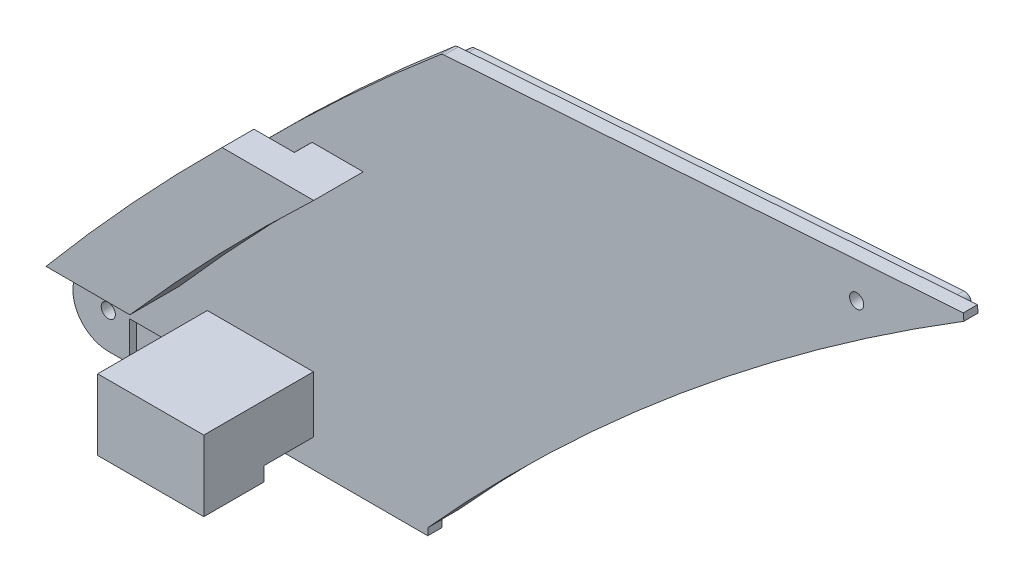
SolidWorks part; units mm, degrees
ref_plane "Front Plane" through (0, 0, 0) normal (0, 0, 1) x (1, 0, 0)
ref_plane "Top Plane" through (0, 0, 0) normal (0, 1, 0) x (1, 0, 0)
ref_plane "Right Plane" through (0, 0, 0) normal (1, 0, 0) x (0, 0, -1)
sketch "Sketch6" plane through (0, 0, 2) normal (0, 0, 1) x (1, 0, 0)
  line L0 (-47.1688, -59) -> (-2.4436, -59) construction
  line L1 (69.7935, 3.878) -> (0.7233, -0.9519) construction
  line L2 (-47.1688, -59) -> (-2.4436, -59)
  line L3 (69.7935, 3.878) -> (0.7233, -0.9519)
  line L4 (-47.1688, -58) -> (-2.4436, -58)
  line L5 (69.8632, 2.8804) -> (0.793, -1.9494)
  arc A0 (-2.4436, -59) -> (-1.7027, -58.6716) centre (-2.4436, -58) ccw construction
  arc A1 (-50.2623, -52.4643) -> (-47.1688, -59) centre (-47.1688, -55) ccw construction
  arc A2 (73.7864, 4.1572) -> (-2, -59) centre (258.3719, -294.388) ccw construction
  arc A3 (70.3988, 2.0359) -> (69.7935, 3.878) centre (69.8632, 2.8804) ccw construction
  arc A4 (0.7233, -0.9519) -> (0.146, -1.187) centre (0.793, -1.9494) ccw construction
  arc A5 (0.146, -1.187) -> (-50.2623, -52.4643) centre (258.3207, -305.4021) ccw construction
  arc A6 (-2.4436, -59) -> (-1.7027, -58.6716) centre (-2.4436, -58) ccw
  arc A7 (-50.2623, -52.4643) -> (-47.1688, -59) centre (-47.1688, -55) ccw
  arc A8 (70.3988, 2.0359) -> (-1.7027, -58.6716) centre (258.3719, -294.388) ccw
  arc A9 (70.3988, 2.0359) -> (69.7935, 3.878) centre (69.8632, 2.8804) ccw
  arc A10 (0.7233, -0.9519) -> (0.146, -1.187) centre (0.793, -1.9494) ccw
  arc A11 (0.146, -1.187) -> (-50.2623, -52.4643) centre (258.3207, -305.4021) ccw
  arc A12 (69.8632, 2.8804) -> (-2.4436, -58) centre (258.3719, -294.388) ccw
  arc A13 (-2.4436, -58) -> (-2.4436, -58) centre (-2.4436, -58) ccw
  arc A14 (-49.4889, -53.0982) -> (-47.1688, -58) centre (-47.1688, -55) ccw
  arc A15 (0.793, -1.9494) -> (-49.4889, -53.0982) centre (258.3207, -305.4021) ccw
  arc A16 (0.793, -1.9494) -> (0.793, -1.9494) centre (0.793, -1.9494) ccw
  arc A17 (69.8632, 2.8804) -> (69.8632, 2.8804) centre (69.8632, 2.8804) ccw
  dimension "D1" = 1
extrude "Boss-Extrude2" add sketch "Sketch6" along normal blind 2
sketch "Sketch7" plane through (0, 0, 4) normal (0, 0, 1) x (1, 0, 0)
  line L0 (73.7167, 5.1548) -> (0.3265, 0.0228) construction
  line L1 (73.7864, 4.1572) -> (73.7167, 5.1548) construction
  line L2 (-2, -59) -> (-2, -60) construction
  line L3 (-47.1688, -60) -> (-2, -60) construction
  line L4 (73.7167, 5.1548) -> (0.3265, 0.0228)
  line L5 (73.7864, 4.1572) -> (73.7167, 5.1548)
  line L6 (-2, -59) -> (-2, -60)
  line L7 (-47.1688, -60) -> (-2, -60)
  arc A0 (0.3265, 0.0228) -> (-0.2501, -0.2118) centre (0.3963, -0.9747) ccw construction
  arc A1 (73.7864, 4.1572) -> (-2, -59) centre (258.3719, -294.388) ccw construction
  arc A2 (-51.0357, -51.8304) -> (-47.1688, -60) centre (-47.1688, -55) ccw construction
  arc A3 (-0.2501, -0.2118) -> (-51.0357, -51.8304) centre (258.3207, -305.4021) ccw construction
  arc A4 (0.3265, 0.0228) -> (-0.2501, -0.2118) centre (0.3963, -0.9747) ccw
  arc A5 (73.7864, 4.1572) -> (-2, -59) centre (258.3719, -294.388) ccw
  arc A6 (-51.0357, -51.8304) -> (-47.1688, -60) centre (-47.1688, -55) ccw
  arc A7 (-0.2501, -0.2118) -> (-51.0357, -51.8304) centre (258.3207, -305.4021) ccw
  circle A8 centre (58.6292, -0.9125) radius 1 construction
  circle A9 centre (-47.1688, -55) radius 1 construction
  circle A10 centre (58.6292, -0.9125) radius 1
  circle A11 centre (-47.1688, -55) radius 1
extrude "Boss-Extrude3" add sketch "Sketch7" along normal blind 2
fillet "Fillet1" radius 2 3 edges at (-2.4436, -58, 3) (0.793, -1.9494, 3) (69.8632, 2.8804, 3)
sketch "Sketch8" plane through (0, 0, 6) normal (0, 0, 1) x (1, 0, 0)
  line L0 (-47.1688, -60) -> (-2, -60) construction
  line L1 (-33.1688, -56) -> (-18.1688, -56)
  line L2 (-33.1688, -56) -> (-33.1688, -48)
  line L3 (-33.1688, -48) -> (-18.1688, -48)
  line L4 (-18.1688, -56) -> (-18.1688, -48)
  arc A0 (-51.0357, -51.8304) -> (-47.1688, -60) centre (-47.1688, -55) ccw construction
  dimension "D1" = 4
  dimension "D2" = 15
  dimension "D3" = 14
  dimension "D4" = 8
extrude "Bottom screwhole peg" add sketch "Sketch8" along normal blind 15.5
sketch "Sketch12" plane through (0, -56, 0) normal (0, -1, 0) x (1, 0, 0)
  line L0 (-18.1688, 21.5) -> (-18.1688, 6) construction
  line L1 (-33.1688, 21.5) -> (-18.1688, 21.5)
  line L2 (-33.1688, 21.5) -> (-33.1688, 13)
  line L3 (-33.1688, 13) -> (-18.1688, 13)
  line L4 (-18.1688, 21.5) -> (-18.1688, 13)
  line L5 (-33.1688, 6) -> (-18.1688, 6) construction
  dimension "D1" = 7
extrude "Bottom clip" add sketch "Sketch12" along normal blind 2
sketch "Sketch9" plane through (0, 0, 6) normal (0, 0, 1) x (1, 0, 0)
  line L0 (-33.1688, -48) -> (-33.1688, -58) construction
  line L1 (-44.1688, -54.5) -> (-35.1688, -54.5)
  line L2 (-44.1688, -54.5) -> (-44.1688, -60)
  line L3 (-44.1688, -60) -> (-35.1688, -60)
  line L4 (-35.1688, -54.5) -> (-35.1688, -60)
  line L5 (-47.1688, -60) -> (-2, -60) construction
  point P6 (-35.1688, -60)
  dimension "D1" = 9
  dimension "D2" = 5.5
  dimension "D3" = 2
extrude "Bumper feature cutout" cut sketch "Sketch9" against normal blind 1
sketch "Sketch10" plane through (0, 0, 6) normal (0, 0, 1) x (1, 0, 0)
  line L0 (-18.3595, -20) -> (-11.1267, -20)
  line L1 (-43.73, -47) -> (-37.119, -47)
  line L2 (-35.1688, -60) -> (-2, -60) construction
  arc A1 (-11.1267, -20) -> (-37.119, -47) centre (258.3207, -305.4021) ccw
  arc A2 (1.3659, -2.1192) -> (-49.1022, -53.4152) centre (258.3207, -305.4021) ccw
  arc A3 (-18.3595, -20) -> (-43.73, -47) centre (258.3207, -305.4021) ccw
  arc A4 (1.3659, -2.1192) -> (-49.1022, -53.4152) centre (258.3207, -305.4021) ccw construction
  arc A5 (4.5981, -5.9341) -> (-45.2353, -56.5848) centre (258.3207, -305.4021) ccw construction
  dimension "D3" = 13
  dimension "D4" = 40
  dimension "D1" = 2.5
  dimension "D2" = 5
extrude "Front clip peg" add sketch "Sketch10" along normal blind 7
sketch "Sketch11" plane through (0, 0, 13) normal (0, 0, 1) x (1, 0, 0)
  line L0 (-43.73, -47) -> (-48.975, -47)
  line L1 (-18.3595, -20) -> (-24.076, -20)
  line L2 (-43.73, -47) -> (-37.119, -47)
  line L3 (-11.1267, -20) -> (-18.3595, -20)
  line L4 (-43.73, -47) -> (-37.119, -47)
  line L5 (-11.1267, -20) -> (-18.3595, -20)
  circle A1 centre (258.3207, -305.4021) radius 397.5 construction
  arc A2 (-18.3595, -20) -> (-43.73, -47) centre (258.3207, -305.4021) ccw
  arc A3 (-11.1267, -20) -> (-37.119, -47) centre (258.3207, -305.4021) ccw
  arc A5 (-11.1267, -20) -> (-37.119, -47) centre (258.3207, -305.4021) ccw
  arc A6 (-18.3595, -20) -> (-43.73, -47) centre (258.3207, -305.4021) ccw construction
  arc A7 (-24.076, -20) -> (-48.975, -47) centre (258.3207, -305.4021) ccw
  circle A8 centre (258.3207, -305.4021) radius 401.5 construction
  dimension "D1" = 0
  dimension "D2" = 4
extrude "Front clip" add sketch "Sketch11" against normal blind 4.5
